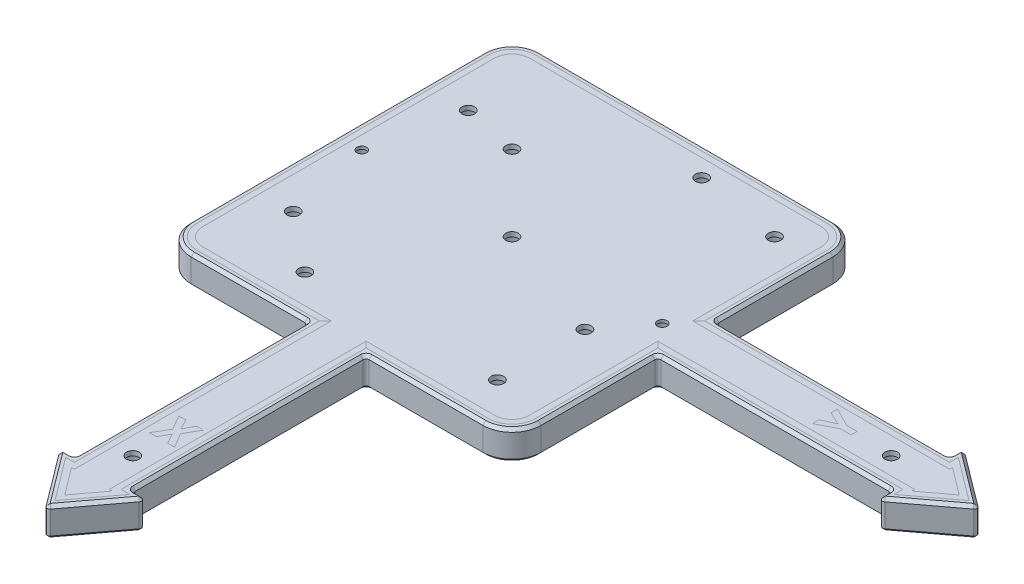
SolidWorks part; units mm, degrees
note: The reader was unsure of these and kept them because the rebuilt part matched: shared geometry of "Sketch7<3>", "Sketch7<4>", "Sketch7<5>", "Sketch7<6>", "Sketch7<7>", "Sketch8<2>", "Sketch9<2>".
ref_plane "Front Plane" through (0, 0, 0) normal (0, 0, 1) x (1, 0, 0)
ref_plane "Top Plane" through (0, 0, 0) normal (0, 1, 0) x (1, 0, 0)
ref_plane "Right Plane" through (0, 0, 0) normal (1, 0, 0) x (0, 0, -1)
sketch "Sketch1" plane through (0, 0, 0) normal (0, 1, 0) x (1, 0, 0)
  line L0 (-10, -60) -> (-10, -140)
  line L1 (-60, -60) -> (-10, -60)
  line L2 (-60, -60) -> (-60, 60)
  line L3 (-60, 60) -> (60, 60)
  line L4 (60, -60) -> (60, -10)
  line L5 (-60, -60) -> (60, 60) construction
  line L6 (-60, 60) -> (60, -60) construction
  line L7 (-10, -140) -> (10, -140)
  line L8 (10, -140) -> (10, -60)
  line L9 (60, -10) -> (140, -10)
  line L10 (140, -10) -> (140, 10)
  line L11 (140, 10) -> (60, 10)
  line L12 (0, 0) -> (140, 0) construction
  line L13 (0, 0) -> (0, -140) construction
  line L14 (10, -60) -> (60, -60)
  line L15 (60, 10) -> (60, 60)
  point P0 (0, 0)
  point P12 (140, 0)
  point P16 (0, -140)
  dimension "D1" = 120
  dimension "D2" = 20
  dimension "D3" = 80
  dimension "D4" = 120
extrude "Boss-Extrude1" add sketch "Sketch1" along normal blind 10
sketch "Sketch2" plane through (0, 10, 0) normal (0, 1, 0) x (1, 0, 0)
  line L0 (0, 0) -> (140, 0) construction
  line L1 (140, -10) -> (140, 10) construction
  line L2 (0, 0) -> (0, -140) construction
  line L3 (-10, -140) -> (10, -140) construction
  circle A0 centre (0, 0) radius 2.15
  circle A1 centre (130, 0) radius 2.15
  circle A2 centre (0, -130) radius 2.15
  circle A3 centre (40, -45) radius 2.15
  circle A4 centre (-45, -30) radius 2.15
  circle A5 centre (-26, 26) radius 2.15
  circle A6 centre (45, 45) radius 2.15
  circle A7 centre (15, 50) radius 2.15
  circle A8 centre (40, -15) radius 2.15
  circle A9 centre (-25, -46) radius 2.15
  circle A10 centre (-45, 30) radius 2.15
  point P29 (0, 0)
  point P30 (0, 0)
  point P31 (15.4415, 48.1084)
  point P33 (2.1263, 0.3182)
  dimension "D1" = 4.3
  dimension "D12" = 50
  dimension "D2" = 130
  dimension "D3" = 130
  dimension "D4" = 40
  dimension "D5" = 45
  dimension "D6" = 45
  dimension "D7" = 30
  dimension "D8" = 26
  dimension "D9" = 26
  dimension "D10" = 45
  dimension "D11" = 45
  dimension "D13" = 15
  dimension "D14" = 30
  dimension "D15" = 45
  dimension "D16" = 46
  dimension "D17" = 25
  dimension "D18" = 40
  dimension "D19" = 15
extrude "Cut-Extrude1" cut sketch "Sketch2" against normal through all
sketch "Sketch3" plane through (0, 10, 0) normal (0, 1, 0) x (1, 0, 0)
  line L0 (-51.5, 0) -> (51.5, 0) construction
  circle A0 centre (51.5, 0) radius 1.65
  circle A1 centre (-51.5, 0) radius 1.65
  point P5 (0, 0)
  point P9 (0, 0)
  dimension "D2" = 3.3
  dimension "D1" = 103
extrude "Cut-Extrude2" cut sketch "Sketch3" against normal through all
sketch "Sketch4" plane through (0, 0, 0) normal (0, -1, 0) x (1, 0, 0)
  circle A0 centre (-45, 30) radius 5
  circle A1 centre (40, 45) radius 5
  circle A2 centre (0, 130) radius 5
  circle A3 centre (130, 0) radius 5
  circle A4 centre (0, 0) radius 5
  circle A5 centre (-26, -26) radius 5
  circle A6 centre (45, -45) radius 5
  circle A7 centre (40, 15) radius 5
  circle A8 centre (-25, 46) radius 5
  circle A9 centre (-45, -30) radius 5
  circle A10 centre (15, -50) radius 5
  dimension "D1" = 10
extrude "Cut-Extrude3" cut sketch "Sketch4" against normal offset from surface (8.4 mm away) 1.6 up to face at (51.5, 10, 1.65)
sketch "Sketch5" plane through (0, 0, 0) normal (0, -1, 0) x (1, 0, 0)
  circle A0 centre (-51.5, 0) radius 3
  circle A1 centre (51.5, 0) radius 3
  dimension "D1" = 6
extrude "Cut-Extrude4" cut sketch "Sketch5" against normal offset from surface (9 mm away) 1 up to face at (51.5, 10, 1.65)
fillet "Fillet1" radius 10 4 edges at (-60, 5, -60) (60, 5, -60) (-60, 5, 60) (60, 5, 60)
sketch "Sketch6" plane through (0, 10, 0) normal (0, 1, 0) x (1, 0, 0)
  line L0 (0, -140) -> (0, -160) construction
  line L1 (-10, -140) -> (10, -140) construction
  line L2 (140, 0) -> (160, 0) construction
  line L3 (140, -10) -> (140, 10) construction
  line L4 (0, -140) -> (15, -140)
  line L5 (15, -140) -> (0, -160)
  line L6 (0, -160) -> (-15, -140)
  line L7 (-15, -140) -> (0, -140)
  line L8 (140, 0) -> (140, -15)
  line L9 (140, -15) -> (160, 0)
  line L10 (160, 0) -> (140, 15)
  line L11 (140, 15) -> (140, 0)
  dimension "D1" = 15
  dimension "D2" = 20
extrude "Boss-Extrude2" add sketch "Sketch6" against normal up to surface (10 mm away) up to face at (-51.5, 0, -3)
sketch "Sketch7" plane through (0, 10, 0) normal (0, 1, 0) x (1, 0, 0)
  line L36 (50, 58) -> (-50, 58)
  line L37 (-58, 50) -> (-58, -50)
  line L38 (-50, -58) -> (-8, -58)
  line L39 (-8, -58) -> (-8, -142)
  line L40 (-8, -142) -> (-11, -142)
  line L41 (-11, -142) -> (0, -156.6667)
  line L42 (0, -156.6667) -> (11, -142)
  line L43 (11, -142) -> (8, -142)
  line L44 (8, -142) -> (8, -58)
  line L45 (8, -58) -> (50, -58)
  line L46 (58, -50) -> (58, -8)
  line L47 (58, -8) -> (142, -8)
  line L48 (142, -8) -> (142, -11)
  line L49 (142, -11) -> (156.6667, 0)
  line L50 (156.6667, 0) -> (142, 11)
  line L51 (142, 11) -> (142, 8)
  line L52 (142, 8) -> (58, 8)
  line L53 (58, 8) -> (58, 50)
  line L54 (50, 58) -> (-50, 58)
  line L55 (-58, 50) -> (-58, -50)
  line L56 (-50, -58) -> (-8, -58)
  line L57 (-8, -58) -> (-8, -142)
  line L58 (-8, -142) -> (-11, -142)
  line L59 (-11, -142) -> (0, -156.6667)
  line L60 (0, -156.6667) -> (11, -142)
  line L61 (11, -142) -> (8, -142)
  line L62 (8, -142) -> (8, -58)
  line L63 (8, -58) -> (50, -58)
  line L64 (58, -50) -> (58, -8)
  line L65 (58, -8) -> (142, -8)
  line L66 (142, -8) -> (142, -11)
  line L67 (142, -11) -> (156.6667, 0)
  line L68 (156.6667, 0) -> (142, 11)
  line L69 (142, 11) -> (142, 8)
  line L70 (142, 8) -> (58, 8)
  line L71 (58, 8) -> (58, 50)
  line L72 (-6, -56) -> (-8, -58)
  line L73 (8, -58) -> (6, -56)
  line L74 (56, -6) -> (58, -8)
  line L75 (58, 8) -> (56, 6)
  line L90 (50, 56) -> (-50, 56)
  line L91 (-56, 50) -> (-56, -50)
  line L92 (-50, -56) -> (-6, -56)
  line L93 (-6, -56) -> (-6, -144)
  line L94 (-6, -144) -> (-7, -144)
  line L95 (-7, -144) -> (0, -153.3333)
  line L96 (0, -153.3333) -> (7, -144)
  line L97 (7, -144) -> (6, -144)
  line L98 (6, -144) -> (6, -56)
  line L99 (6, -56) -> (50, -56)
  line L100 (56, -50) -> (56, -6)
  line L101 (56, -6) -> (144, -6)
  line L102 (144, -6) -> (144, -7)
  line L103 (144, -7) -> (153.3333, 0)
  line L104 (153.3333, 0) -> (144, 7)
  line L105 (144, 7) -> (144, 6)
  line L106 (144, 6) -> (56, 6)
  line L107 (56, 6) -> (56, 50)
  line L108 (50, 56) -> (-50, 56)
  line L109 (-56, 50) -> (-56, -50)
  line L110 (-50, -56) -> (-6, -56)
  line L111 (-6, -56) -> (-6, -144)
  line L112 (-6, -144) -> (-7, -144)
  line L113 (-7, -144) -> (0, -153.3333)
  line L114 (0, -153.3333) -> (7, -144)
  line L115 (7, -144) -> (6, -144)
  line L116 (6, -144) -> (6, -56)
  line L117 (6, -56) -> (50, -56)
  line L118 (56, -50) -> (56, -6)
  line L119 (56, -6) -> (144, -6)
  line L120 (144, -6) -> (144, -7)
  line L121 (144, -7) -> (153.3333, 0)
  line L122 (153.3333, 0) -> (144, 7)
  line L123 (144, 7) -> (144, 6)
  line L124 (144, 6) -> (56, 6)
  line L125 (56, 6) -> (56, 50)
  arc A8 (-50, 58) -> (-58, 50) centre (-50, 50) ccw
  arc A9 (-58, -50) -> (-50, -58) centre (-50, -50) ccw
  arc A10 (50, -58) -> (58, -50) centre (50, -50) ccw
  arc A11 (58, 50) -> (50, 58) centre (50, 50) ccw
  arc A12 (-50, 58) -> (-58, 50) centre (-50, 50) ccw
  arc A13 (-58, -50) -> (-50, -58) centre (-50, -50) ccw
  arc A14 (50, -58) -> (58, -50) centre (50, -50) ccw
  arc A15 (58, 50) -> (50, 58) centre (50, 50) ccw
  arc A20 (-50, 56) -> (-56, 50) centre (-50, 50) ccw
  arc A21 (-56, -50) -> (-50, -56) centre (-50, -50) ccw
  arc A22 (50, -56) -> (56, -50) centre (50, -50) ccw
  arc A23 (56, 50) -> (50, 56) centre (50, 50) ccw
  arc A24 (-50, 56) -> (-56, 50) centre (-50, 50) ccw
  arc A25 (-56, -50) -> (-50, -56) centre (-50, -50) ccw
  arc A26 (50, -56) -> (56, -50) centre (50, -50) ccw
  arc A27 (56, 50) -> (50, 56) centre (50, 50) ccw
  dimension "D1" = 2
  dimension "D2" = 4
extrude "Cut-Extrude5" cut sketch "Sketch7" against normal blind 1 contours L116 L115 L114 L113 L112 L111 L72 L57 L58 L59 L60 L61 L62 L73
extrude "Boss-Extrude3" add sketch "Sketch7<3>" against normal up to surface (1 mm away) separate body contours L116 L115 L114 L113 L112 L111 L72 L57 L58 L59 L60 L61 L62 L73 up to face at (0, 9, 120.1429)
sketch "Sketch7<3>" plane through (0, 10, 0) normal (0, 1, 0) x (1, 0, 0) same geometry as "Sketch7"
extrude "Cut-Extrude6" cut sketch "Sketch7<4>" against normal blind 1 contours L124 L123 L122 L121 L120 L119 L74 L65 L66 L67 L68 L69 L70 L75
sketch "Sketch7<4>" plane through (0, 10, 0) normal (0, 1, 0) x (1, 0, 0) same geometry as "Sketch7"
extrude "Boss-Extrude4" add sketch "Sketch7<5>" against normal up to surface (1 mm away) separate body contours L124 L123 L122 L121 L120 L119 L74 L65 L66 L67 L68 L69 L70 L75 up to face at (120.1429, 9, 0)
sketch "Sketch7<5>" plane through (0, 10, 0) normal (0, 1, 0) x (1, 0, 0) same geometry as "Sketch7"
extrude "Cut-Extrude7" cut sketch "Sketch7<6>" against normal blind 1 contours A27 L125 L75 L71 A15 L54 A12 L55 A13 L56 L72 L110 A25 L109 A24 L108 | A26 L117 L73 L63 A14 L64 L74 L118
sketch "Sketch7<6>" plane through (0, 10, 0) normal (0, 1, 0) x (1, 0, 0) same geometry as "Sketch7"
extrude "Boss-Extrude5" add sketch "Sketch7<7>" against normal up to surface (1 mm away) separate body contours A27 L125 L75 L71 A15 L54 A12 L55 A13 L56 L72 L110 A25 L109 A24 L108 | A26 L117 L73 L63 A14 L64 L74 L118 up to face at (38.2424, 9, 38.2424)
sketch "Sketch7<7>" plane through (0, 10, 0) normal (0, 1, 0) x (1, 0, 0) same geometry as "Sketch7"
fillet "Fillet2" radius 1 14 edges at (60, 5, -10) (-10, 5, 60) (10, 5, 60) (60, 5, 10) (140, 5, 15) (140, 5, 10) (140, 5, -15) (140, 5, -10) (160, 5, 0) (-10, 5, 140) (-15, 5, 140) (0, 5, 160) (10, 5, 140) (15, 5, 140)
chamfer "Chamfer1" distance 1 angle 45 72 edges at (10, 0, 100) (10, 10, 100) (10.2929, 10, 60.2929) (10.2929, 0, 60.2929) (10.2929, 10, 139.7071) (10.2929, 0, 139.7071) (30.5, 10, 60) (30.5, 0, 60) (12, 0, 140) (57.0711, 10, 57.0711) (57.0711, 0, 57.0711) (13.8944, 0, 140.5528) (13.8944, 10, 140.5528) (60, 0, 30.5) (60, 10, 30.5) (7.3, 0, 150.2667) (60.2929, 10, 10.2929) (60.2929, 0, 10.2929) (0, 0, 159.3333) (0, 10, 159.3333) (100, 10, 10) (100, 0, 10) (-7.3, 0, 150.2667) (139.7071, 10, 10.2929) (139.7071, 0, 10.2929) (-13.8944, 0, 140.5528) (-13.8944, 10, 140.5528) (140, 0, 12) (-12, 0, 140) (140.5528, 0, 13.8944) (140.5528, 10, 13.8944) (-10.2929, 10, 139.7071) (-10.2929, 0, 139.7071) (150.2667, 0, 7.3) (-10, 10, 100) (-10, 0, 100) (159.3333, 0, 0) (159.3333, 10, 0) (-10.2929, 10, 60.2929) (-10.2929, 0, 60.2929) (150.2667, 0, -7.3) (-30.5, 0, 60) (-30.5, 10, 60) (140.5528, 0, -13.8944) (140.5528, 10, -13.8944) (-57.0711, 10, 57.0711) (-57.0711, 0, 57.0711) (140, 0, -12) (-60, 10, 0) (-60, 0, 0) (139.7071, 10, -10.2929) (139.7071, 0, -10.2929) (-57.0711, 10, -57.0711) (-57.0711, 0, -57.0711) (100, 0, -10) (100, 10, -10) (0, 0, -60) (0, 10, -60) (60.2929, 10, -10.2929) (60.2929, 0, -10.2929) (57.0711, 10, -57.0711) (57.0711, 0, -57.0711) (60, 10, -30.5) (60, 0, -30.5) (140, 10, -12) (-12, 10, 140) (150.2667, 10, -7.3) (-7.3, 10, 150.2667) (150.2667, 10, 7.3) (7.3, 10, 150.2667) (140, 10, 12) (12, 10, 140)
sketch "Sketch8" plane through (0, 10, 0) normal (0, 1, 0) x (1, 0, 0)
  line L0 (-4.1302, -120.3099) -> (3.9673, -120.3099) construction
  text T0 "X" font "Roboto" height 10
extrude "Cut-Extrude8" cut sketch "Sketch8" against normal blind 1
extrude "Boss-Extrude6" add sketch "Sketch8<2>" against normal up to surface (1 mm away) separate body up to face at (0.3282, 9, 115.2986)
sketch "Sketch8<2>" plane through (0, 10, 0) normal (0, 1, 0) x (1, 0, 0) same geometry as "Sketch8"
sketch "Sketch9" plane through (0, 10, 0) normal (0, 1, 0) x (1, 0, 0)
  line L0 (116.9469, -4) -> (116.9469, 3.8639) construction
  line L1 (56, -6) -> (144, -6) construction
  text T0 "Y" font "Roboto" height 10
  dimension "D1" = 2
extrude "Cut-Extrude9" cut sketch "Sketch9" against normal blind 1
extrude "Boss-Extrude7" add sketch "Sketch9<2>" against normal up to surface (1 mm away) separate body up to face at (111.0861, 9, -0.3322)
sketch "Sketch9<2>" plane through (0, 10, 0) normal (0, 1, 0) x (1, 0, 0) same geometry as "Sketch9"
